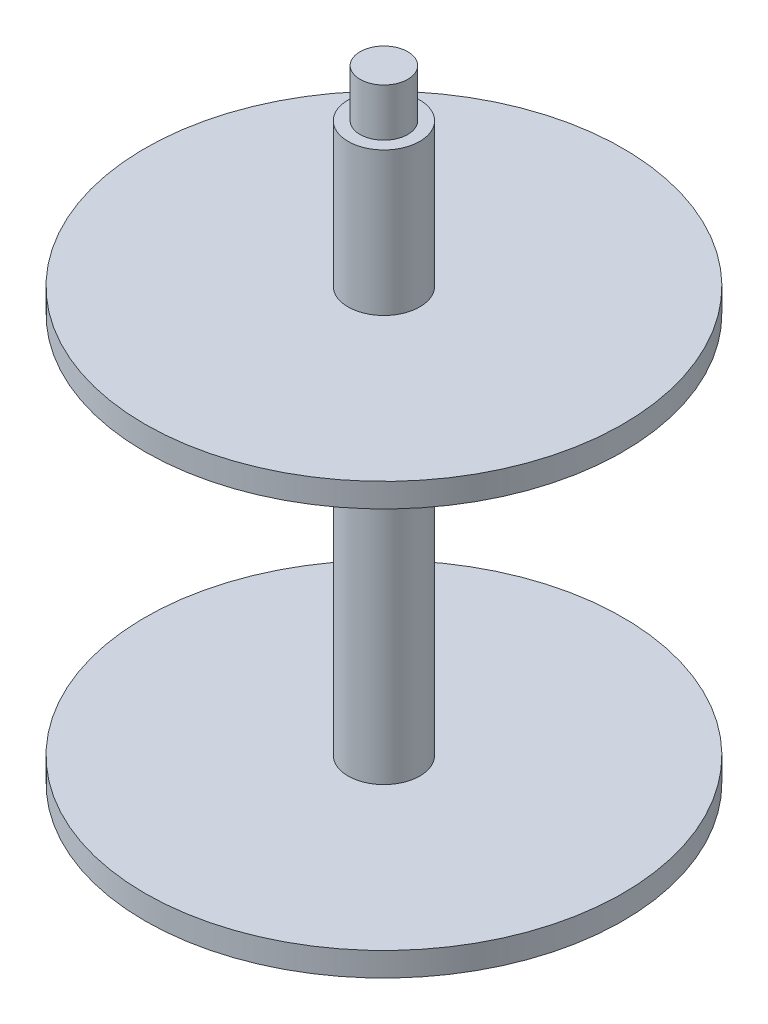
SolidWorks part; units mm, degrees
ref_plane "Front Plane" through (0, 0, 0) normal (0, 0, 1) x (1, 0, 0)
ref_plane "Top Plane" through (0, 0, 0) normal (0, 1, 0) x (1, 0, 0)
ref_plane "Right Plane" through (0, 0, 0) normal (1, 0, 0) x (0, 0, -1)
sketch "Sketch1" plane through (0, 0, 0) normal (0, 1, 0) x (1, 0, 0)
  circle A0 centre (0, 0) radius 7.5
  circle A1 centre (0, 0) radius 50
  dimension "D1" = 15
  dimension "D2" = 100
extrude "Boss-Extrude1" add sketch "Sketch1" along normal blind 160 contours A0 region at (0, 0, 0)
extrude "Boss-Extrude2" add sketch "Sketch1<3>" against normal blind 5 from offset 35 contours A1
sketch "Sketch1<3>" plane through (0, 0, 0) normal (0, 1, 0) x (1, 0, 0) same geometry as "Sketch1"
extrude "Boss-Extrude3" add sketch "Sketch1<4>" along normal blind 5 from offset 115
sketch "Sketch1<4>" plane through (0, 0, 0) normal (0, 1, 0) x (1, 0, 0) same geometry as "Sketch1"
sketch "Sketch2" plane through (0, 160, 0) normal (0, 1, 0) x (1, 0, 0)
  circle A1 centre (0, 0) radius 7.5 construction
  circle A2 centre (0, 0) radius 5
  circle A3 centre (0, 0) radius 5
  circle A4 centre (0, 0) radius 7.5
  dimension "D1" = 2.5
extrude "Cut-Extrude1" cut sketch "Sketch2" against normal blind 10
